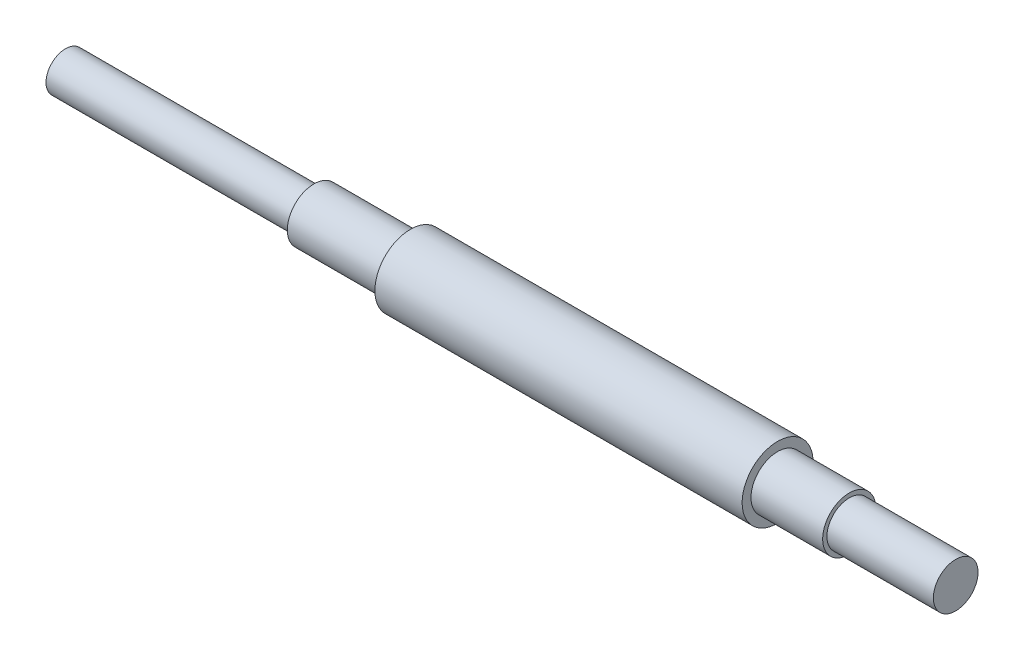
SolidWorks part; units mm, degrees
ref_plane "Front Plane" through (0, 0, 0) normal (0, 0, 1) x (1, 0, 0)
ref_plane "Top Plane" through (0, 0, 0) normal (0, 1, 0) x (1, 0, 0)
ref_plane "Right Plane" through (0, 0, 0) normal (1, 0, 0) x (0, 0, -1)
sketch "Sketch1" plane through (0, 0, 0) normal (0, 1, 0) x (1, 0, 0)
  line L0 (-78.6306, 0) -> (80.6662, 0) construction
  line L1 (-78.6306, 0) -> (-78.6306, 3.5)
  line L2 (-78.6306, 3.5) -> (-34.1806, 3.5)
  line L3 (-34.1806, 3.5) -> (-34.1806, 4.7625)
  line L4 (-34.1806, 4.7625) -> (-16.9251, 4.7625)
  line L5 (-16.9251, 4.7625) -> (-16.9251, 6.35)
  line L6 (-16.9251, 6.35) -> (48.7948, 6.35)
  line L7 (48.7948, 6.35) -> (48.7948, 4.7625)
  line L8 (48.7948, 4.7625) -> (61.6162, 4.7625)
  line L9 (61.6162, 4.7625) -> (61.6162, 3.9992)
  line L10 (61.6162, 3.9992) -> (80.6662, 3.9992)
  line L11 (80.6662, 3.9992) -> (80.6662, 0)
  line L12 (-78.6306, 0) -> (80.6662, 0)
  line L13 (-97.9506, 0) -> (194.5593, 0) construction
  dimension "D1" = 7
  dimension "D2" = 9.525
  dimension "D3" = 9.525
  dimension "D4" = 7.9985
  dimension "D5" = 44.45
  dimension "D6" = 17.2554
  dimension "D7" = 12.8214
  dimension "D8" = 19.05
  dimension "D9" = 65.72
  dimension "D10" = 6.35
revolve "Revolve1" add sketch "Sketch1" angle 360 about L13
